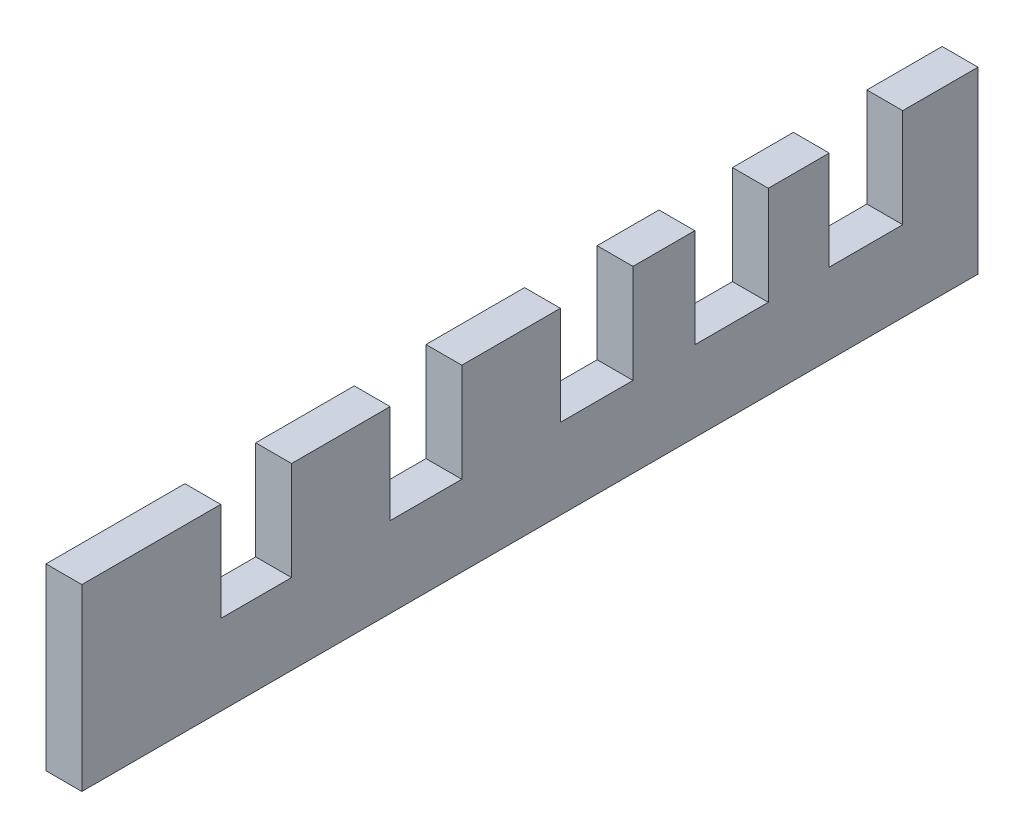
SolidWorks part; units mm, degrees
ref_plane "Front Plane" through (0, 0, 0) normal (0, 0, 1) x (1, 0, 0)
ref_plane "Top Plane" through (0, 0, 0) normal (0, 1, 0) x (1, 0, 0)
ref_plane "Right Plane" through (0, 0, 0) normal (1, 0, 0) x (0, 0, -1)
sketch "Sketch1" plane through (0, 0, 0) normal (0, 0, 1) x (1, 0, 0)
  line L1 (0, 0) -> (5.08, 0)
  line L2 (0, 0) -> (0, 25.4)
  line L3 (0, 25.4) -> (5.08, 25.4)
  line L4 (5.08, 0) -> (5.08, 25.4)
  dimension "D1" = 25.4
  dimension "D2" = 5.08
extrude "Boss-Extrude1" add sketch "Sketch1" along normal blind 127
sketch "Sketch7" plane through (5.08, 0, 0) normal (1, 0, 0) x (0, 0, -1)
  line L0 (-18.542, 25.4) -> (-13.208, 25.4)
  line L1 (-104.775, 25.4) -> (-99.822, 25.4)
  line L5 (-18.542, 25.4) -> (-13.208, 25.4)
  line L6 (-18.542, 25.4) -> (-18.542, 13.9394)
  line L7 (-18.542, 13.9394) -> (-13.208, 13.9394)
  line L8 (-13.208, 25.4) -> (-13.208, 13.9394)
  line L9 (-37.592, 25.4) -> (-32.258, 25.4)
  line L10 (-37.592, 25.4) -> (-37.592, 13.9394)
  line L11 (-37.592, 13.9394) -> (-32.258, 13.9394)
  line L12 (-32.258, 25.4) -> (-32.258, 13.9394)
  line L13 (-56.642, 25.4) -> (-51.435, 25.4)
  line L14 (-56.642, 25.4) -> (-56.642, 13.9394)
  line L15 (-56.642, 13.9394) -> (-51.435, 13.9394)
  line L16 (-51.435, 25.4) -> (-51.435, 13.9394)
  line L17 (-75.692, 25.4) -> (-80.772, 25.4)
  line L18 (-75.692, 25.4) -> (-75.692, 13.9394)
  line L19 (-75.692, 13.9394) -> (-80.772, 13.9394)
  line L20 (-80.772, 25.4) -> (-80.772, 13.9394)
  line L21 (-99.822, 25.4) -> (-104.775, 25.4)
  line L22 (-99.822, 25.4) -> (-99.822, 13.9394)
  line L23 (-99.822, 13.9394) -> (-104.775, 13.9394)
  line L24 (-104.775, 25.4) -> (-104.775, 13.9394)
  line L25 (-37.592, 25.4) -> (-32.258, 25.4)
  line L26 (-56.642, 25.4) -> (-51.435, 25.4)
  line L27 (-80.772, 25.4) -> (-75.692, 25.4)
  point P26 (-37.592, 19.6697)
  line M27 (0, 25.4) -> (-127, 25.4)
  dimension "D2" = 19.05
  dimension "D4" = 19.05
  dimension "D5" = 19.05
  dimension "D6" = 19.05
  dimension "D7" = 5.334
  dimension "D8" = 5.334
  dimension "D9" = 5.207
  dimension "D10" = 5.08
  dimension "D11" = 4.953
extrude "Cut-Extrude-Thin1" cut sketch "Sketch7" against normal through all thin contours L16 L14 L15 M27 | L12 L10 L11 M27 | L8 L6 L7 M27 | L20 L19 L18 M27 | L24 L23 L22 M27 | L6 L7 L8 body kept at (0, 0, 0) thin type one direction wall 2.54
sketch "Sketch8" plane through (0, 0, 0) normal (-1, 0, 0) x (0, 0, 1)
  text T0 ".215"
  text T1 ".195\r\n"
